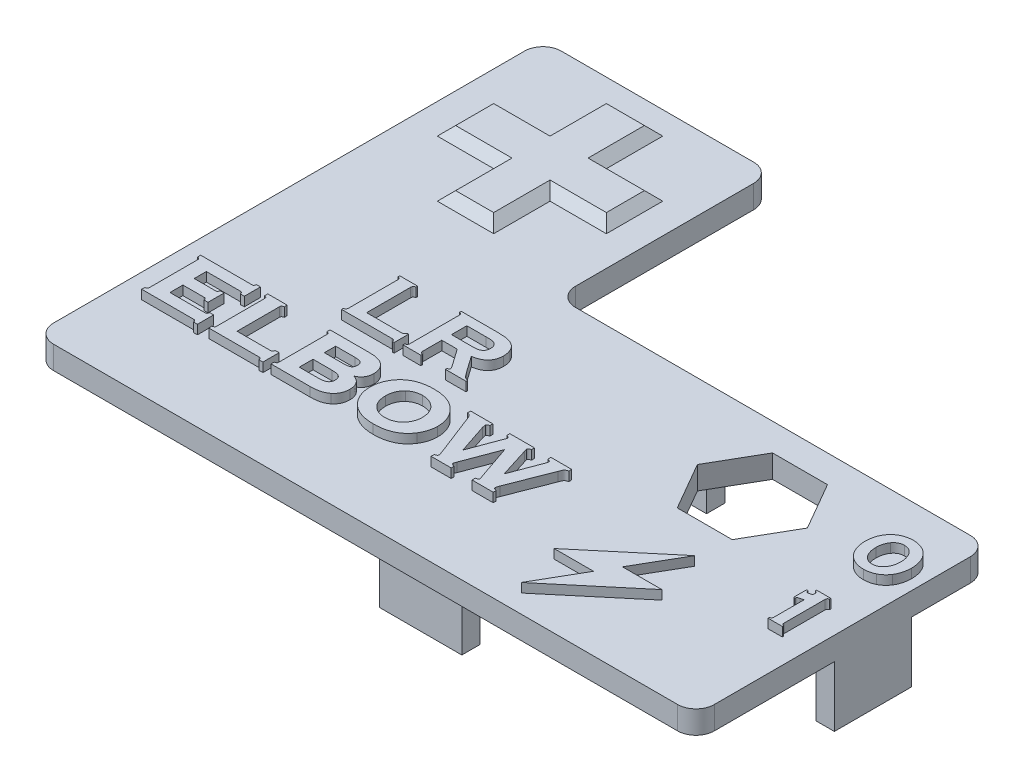
SolidWorks part; units mm, degrees
ref_plane "Front" through (0, 0, 0) normal (0, 0, 1) x (1, 0, 0)
ref_plane "Top" through (0, 0, 0) normal (0, 1, 0) x (1, 0, 0)
ref_plane "Right" through (0, 0, 0) normal (1, 0, 0) x (0, 0, -1)
sketch "Sketch1" plane through (0, 0, 0) normal (0, 1, 0) x (1, 0, 0)
  line L0 (-36.05, 15.975) -> (-36.05, 39.425)
  line L1 (-36.05, -15.975) -> (36.05, -15.975)
  line L2 (-36.05, -15.975) -> (-36.05, 15.975)
  line L3 (-11.05, 15.975) -> (36.05, 15.975)
  line L4 (36.05, -15.975) -> (36.05, 15.975)
  line L5 (-36.05, -15.975) -> (36.05, 15.975) construction
  line L6 (-36.05, 15.975) -> (36.05, -15.975) construction
  line L7 (-36.05, 39.425) -> (-11.05, 39.425)
  line L8 (-11.05, 39.425) -> (-11.05, 15.975)
  point P0 (0, 0)
  dimension "D1" = 31.95
  dimension "D2" = 72.1
  dimension "D3" = 25
  dimension "D4" = 55.4
extrude "Boss-Extrude1" add sketch "Sketch1" along normal blind 2.5
fillet "Fillet1" radius 2 6 edges at (36.05, 1.25, -15.975) (36.05, 1.25, 15.975) (-36.05, 1.25, 15.975) (-11.05, 1.25, -15.975) (-11.05, 1.25, -39.425) (-36.05, 1.25, -39.425)
sketch "Sketch2" plane through (0, 0, 0) normal (0, -1, 0) x (1, 0, 0)
  line L0 (36.05, 13.975) -> (36.05, -13.975) construction
  line L1 (34.05, -7.525) -> (36.05, -7.525)
  line L2 (34.05, -7.525) -> (34.05, 0.875)
  line L3 (34.05, 0.875) -> (36.05, 0.875)
  line L4 (36.05, -7.525) -> (36.05, 0.875)
  line L5 (34.05, -7.525) -> (36.05, 0.875) construction
  line L6 (34.05, 0.875) -> (36.05, -7.525) construction
  line L7 (35.05, -7.575) -> (35.05, 0.925) construction
  line L8 (35.05, 0.925) -> (35.05, 15.975) construction
  line L9 (-34.05, 15.975) -> (34.05, 15.975) construction
  line L10 (34.05, -15.975) -> (-9.05, -15.975) construction
  line L11 (8.5, -14.725) -> (-0.5, -14.725)
  line L12 (8.5, -14.725) -> (8.5, -12.725)
  line L13 (8.5, -12.725) -> (-0.5, -12.725)
  line L14 (-0.5, -14.725) -> (-0.5, -12.725)
  line L15 (8.5, -14.725) -> (-0.5, -12.725) construction
  line L16 (8.5, -12.725) -> (-0.5, -14.725) construction
  line L17 (8.5, 11.975) -> (-0.5, 11.975)
  line L18 (8.5, 11.975) -> (8.5, 13.975)
  line L19 (8.5, 13.975) -> (-0.5, 13.975)
  line L20 (-0.5, 11.975) -> (-0.5, 13.975)
  line L21 (8.5, 11.975) -> (-0.5, 13.975) construction
  line L22 (8.5, 13.975) -> (-0.5, 11.975) construction
  line L23 (0, 0) -> (-50000, 0) construction
  point P0 (35.05, -3.325)
  point P7 (35.05, -3.325)
  point P13 (4, -13.725)
  point P18 (4, 12.975)
  dimension "D1" = 2
  dimension "D2" = 8.4
  dimension "D3" = 15.05
  dimension "D4" = 8.5
  dimension "D5" = 2
  dimension "D6" = 1.25
  dimension "D7" = 2
  dimension "D8" = 0.5
  dimension "D9" = 9
extrude "Boss-Extrude2" add sketch "Sketch2" along normal blind 6.6
sketch "Sketch3" plane through (0, 2.5, 0) normal (0, 1, 0) x (1, 0, 0)
  line L0 (-21.55, 2.025) -> (-6.55, 2.025) construction
  line L1 (-34.05, -6.975) -> (5.95, -6.975) construction
  line L2 (29.55, 6.025) -> (36.05, 6.025) construction
  line L9 (21.9141, -1.975) -> (19.0274, -6.975)
  line L11 (17.8726, -8.975) -> (14.9859, -13.975)
  line L12 (14.9859, -13.975) -> (23.3282, -6.975)
  line L13 (23.3282, -6.975) -> (19.0274, -6.975)
  line L14 (21.9141, -1.975) -> (13.5718, -8.975)
  line L15 (13.5718, -8.975) -> (17.8726, -8.975)
  line L16 (12.7, -15.975) -> (12.7, 0.025) construction
  line L17 (-34.05, -15.975) -> (34.05, -15.975) construction
  line L18 (12.7, 0.025) -> (24.2, 0.025) construction
  line L19 (24.2, 0.025) -> (24.2, -15.975) construction
  line L20 (24.2, -15.975) -> (12.7, -15.975) construction
  line L21 (36.05, -13.975) -> (36.05, 13.975) construction
  line L22 (21.9141, -1.975) -> (14.9859, -13.975) construction
  line L23 (-26.625, 36.925) -> (-20.475, 36.925)
  line L24 (-20.475, 36.925) -> (-20.475, 30.775)
  line L25 (-36.05, 37.425) -> (-36.05, -13.975) construction
  line L26 (-20.475, 30.775) -> (-14.325, 30.775)
  line L27 (-14.325, 30.775) -> (-14.325, 24.625)
  line L28 (-14.325, 24.625) -> (-20.475, 24.625)
  line L29 (-20.475, 24.625) -> (-20.475, 18.475)
  line L30 (-20.475, 18.475) -> (-26.625, 18.475)
  line L31 (-26.625, 18.475) -> (-26.625, 24.625)
  line L32 (-26.625, 24.625) -> (-32.775, 24.625)
  line L33 (-32.775, 24.625) -> (-32.775, 30.775)
  line L34 (-32.775, 30.775) -> (-26.625, 30.775)
  line L35 (-26.625, 30.775) -> (-26.625, 36.925)
  line L36 (-11.05, 27.7) -> (-36.05, 27.7) construction
  line L37 (-11.05, 17.975) -> (-11.05, 37.425) construction
  line L38 (-36.05, 37.425) -> (-36.05, -13.975) construction
  line L39 (-13.05, 39.425) -> (-34.05, 39.425) construction
  text T0 "<b>ELBOW</b>" font "Copperplate Gothic Bold" height 6.35
  text T1 "LR" font "Copperplate Gothic Bold" height 6.35
  text T2 "0\r\n1" font "Copperplate Gothic Bold" height in points 26
  point P18 (18.45, -7.975)
  point P19 (18.45, 0.025)
  point P20 (12.7, -7.975)
  point P38 (-32.775, 27.7)
  point P43 (-14.05, 2.025)
  point P44 (-14.05, -6.975)
  point P50 (-23.55, 36.925)
  point P51 (-23.55, 27.7)
  dimension "D1" = 40
  dimension "D2" = 20
  dimension "D3" = 2
  dimension "D4" = 5
  dimension "D5" = 11.85
  dimension "D6" = 23.35
  dimension "D7" = 2
  dimension "D8" = 6.5
  dimension "D9" = 22
  dimension "D10" = 18
  dimension "D11" = 2
  dimension "D12" = 9
  dimension "D13" = 40
  dimension "D14" = 15
  dimension "D15" = 2.5
extrude "Boss-Extrude3" add sketch "Sketch3" along normal blind 1
sketch "Sketch4" plane through (0, 2.5, 0) normal (0, 1, 0) x (1, 0, 0)
  line L5 (34.05, 15.975) -> (-9.05, 15.975) construction
  line L7 (18.45, 2.5827) -> (18.45, -15.975) construction
  line L9 (21.45, 2.5827) -> (24.45, 7.7788)
  line L10 (24.45, 7.7788) -> (21.45, 12.975)
  line L11 (21.45, 12.975) -> (15.45, 12.975)
  line L12 (15.45, 12.975) -> (12.45, 7.7788)
  line L13 (12.45, 7.7788) -> (15.45, 2.5827)
  line L14 (15.45, 2.5827) -> (21.45, 2.5827)
  line L15 (24.2, -15.975) -> (12.7, -15.975) construction
  circle A0 centre (18.45, 7.7788) radius 5.1962 construction
  dimension "D1" = 3
  dimension "D2" = 6
extrude "Cut-Extrude1" cut sketch "Sketch4" against normal up to vertex (2.5 mm away) up to point (34.05, 0, 15.975)
chamfer "Chamfer1" distance 1 angle 45 12 edges at (-23.55, 3.5, -36.925) (-20.475, 3.5, -33.85) (-17.4, 3.5, -30.775) (-14.325, 3.5, -27.7) (-17.4, 3.5, -24.625) (-20.475, 3.5, -21.55) (-23.55, 3.5, -18.475) (-26.625, 3.5, -21.55) (-29.7, 3.5, -24.625) (-32.775, 3.5, -27.7) (-29.7, 3.5, -30.775) (-26.625, 3.5, -33.85)
